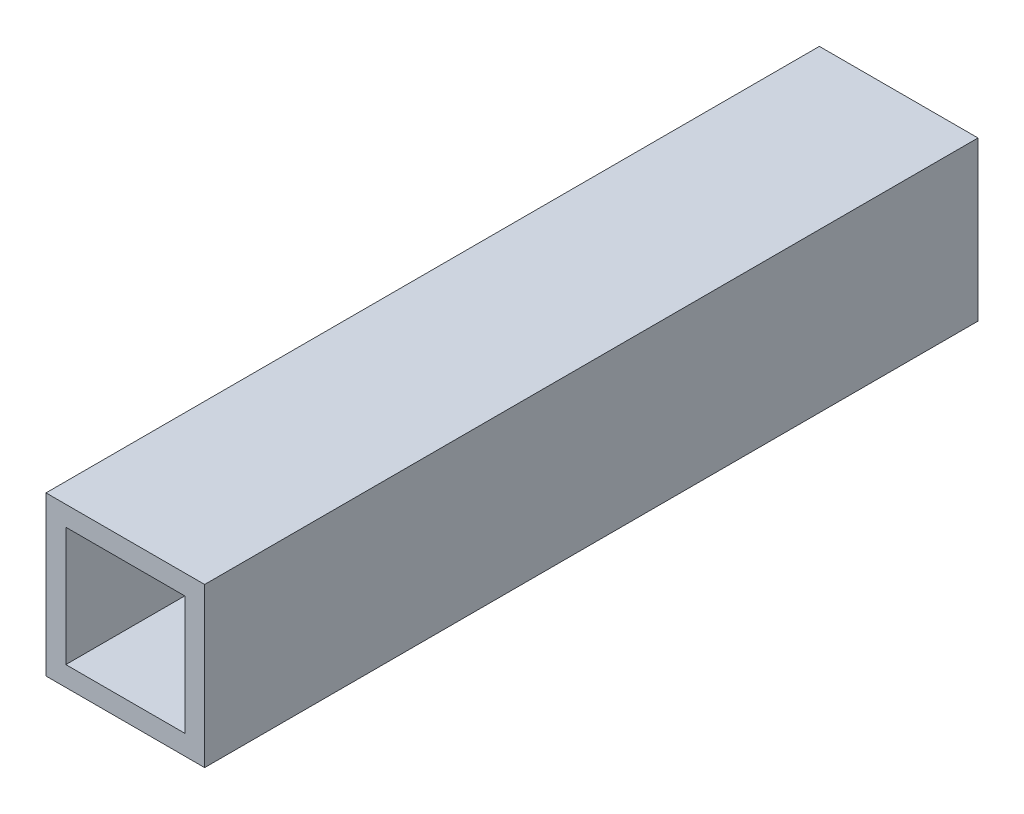
SolidWorks part; units mm, degrees
ref_plane "Front Plane" through (0, 0, 0) normal (0, 0, 1) x (1, 0, 0)
ref_plane "Top Plane" through (0, 0, 0) normal (0, 1, 0) x (1, 0, 0)
ref_plane "Right Plane" through (0, 0, 0) normal (1, 0, 0) x (0, 0, -1)
sketch "Sketch1" plane through (0, 0, 0) normal (0, 0, 1) x (1, 0, 0)
  line L1 (-12.7, -12.7) -> (12.7, -12.7)
  line L2 (-12.7, -12.7) -> (-12.7, 12.7)
  line L3 (-12.7, 12.7) -> (12.7, 12.7)
  line L4 (12.7, -12.7) -> (12.7, 12.7)
  line L5 (-12.7, -12.7) -> (12.7, 12.7) construction
  line L6 (-12.7, 12.7) -> (12.7, -12.7) construction
  point P0 (0, 0)
  dimension "D1" = 25.4
  dimension "D2" = 25.4
extrude "Boss-Extrude1" add sketch "Sketch1" along normal mid plane 123.825
shell "Shell1" thickness 3.175 removed face at (0, 0, -61.9125) removed face at (0, 0, 61.9125)
